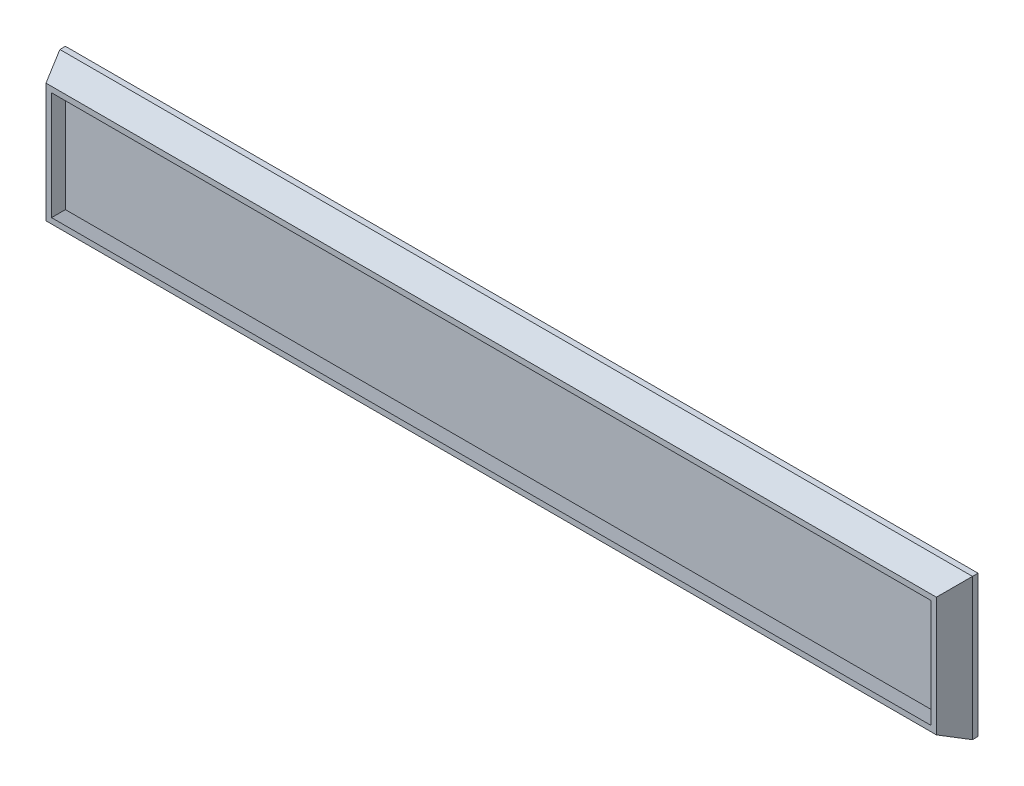
SolidWorks part; units mm, degrees
ref_plane "Płaszczyzna przednia" through (0, 0, 0) normal (0, 0, 1) x (1, 0, 0)
ref_plane "Płaszczyzna górna" through (0, 0, 0) normal (0, 1, 0) x (1, 0, 0)
ref_plane "Płaszczyzna prawa" through (0, 0, 0) normal (1, 0, 0) x (0, 0, -1)
sketch "Szkic1" plane through (0, 0, 0) normal (0, 0, 1) x (1, 0, 0)
  line L1 (-82.25, -12.75) -> (82.25, -12.75)
  line L2 (-82.25, -12.75) -> (-82.25, 12.75)
  line L3 (-82.25, 12.75) -> (82.25, 12.75)
  line L4 (82.25, -12.75) -> (82.25, 12.75)
  line L5 (-82.25, -12.75) -> (82.25, 12.75) construction
  line L6 (-82.25, 12.75) -> (82.25, -12.75) construction
  point P0 (0, 0)
  dimension "D1" = 25.5
  dimension "D2" = 164.5
extrude "Dodanie-wyciągnięcie1" add sketch "Szkic1" along normal blind 1
sketch "Szkic2" plane through (0, 0, 1) normal (0, 0, 1) x (1, 0, 0)
  line L0 (81.25, -11.75) -> (81.25, 11.75)
  line L1 (81.25, 11.75) -> (-81.25, 11.75)
  line L2 (-81.25, 11.75) -> (-81.25, -11.75)
  line L3 (-81.25, -11.75) -> (81.25, -11.75)
  line L4 (82.25, -12.75) -> (82.25, 12.75)
  line L5 (82.25, 12.75) -> (-82.25, 12.75)
  line L6 (-82.25, 12.75) -> (-82.25, -12.75)
  line L7 (-82.25, -12.75) -> (82.25, -12.75)
  line L8 (82.25, -12.75) -> (82.25, 12.75)
  line L9 (82.25, 12.75) -> (-82.25, 12.75)
  line L10 (-82.25, 12.75) -> (-82.25, -12.75)
  line L11 (-82.25, -12.75) -> (82.25, -12.75)
  dimension "D1" = 0
  dimension "D2" = 1
ref_plane "Płaszczyzna1" through (0, 0, 5.5) normal (0, 0, 1) x (1, 0, 0)
sketch "Szkic3" plane through (0, 0, 5.5) normal (0, 0, 1) x (1, 0, 0)
  line L0 (-81.25, -11.75) -> (81.25, -11.75) construction
  line L1 (-81.25, 11.75) -> (-81.25, -11.75) construction
  line L2 (81.25, 11.75) -> (-81.25, 11.75) construction
  line L3 (81.25, -11.75) -> (81.25, 11.75) construction
  line L4 (-81.25, -11.75) -> (81.25, -11.75) construction
  line L5 (-81.25, 11.75) -> (-81.25, -11.75) construction
  line L6 (81.25, 11.75) -> (-81.25, 11.75) construction
  line L7 (81.25, -11.75) -> (81.25, 11.75) construction
  line L8 (-80.25, -10.75) -> (80.25, -10.75)
  line L9 (80.25, -10.75) -> (80.25, 10.75)
  line L10 (80.25, 10.75) -> (-80.25, 10.75)
  line L11 (-80.25, 10.75) -> (-80.25, -10.75)
  line L12 (79.25, -9.75) -> (79.25, 9.75)
  line L13 (79.25, 9.75) -> (-79.25, 9.75)
  line L14 (-79.25, 9.75) -> (-79.25, -9.75)
  line L15 (-79.25, -9.75) -> (79.25, -9.75)
  dimension "D1" = 1
  dimension "D2" = 1
loft "Wyciągnięcie po profilach2" add section "Szkic3" section "Szkic2" connector at (-80.25, -10.75, 5.5) connector at (-82.25, -12.75, 1)
loft "Wycięcie-wyciągnięcie po profilach1" cut section "Szkic3<140>" section "Szkic2<152>" connector at (-79.25, -9.75, 5.5) connector at (-81.25, -11.75, 1)
sketch "Szkic3<140>" plane through (0, 0, 5.5) normal (0, 0, 1) x (1, 0, 0) same geometry as "Szkic3"
sketch "Szkic2<152>" plane through (0, 0, 1) normal (0, 0, 1) x (1, 0, 0) same geometry as "Szkic2"
